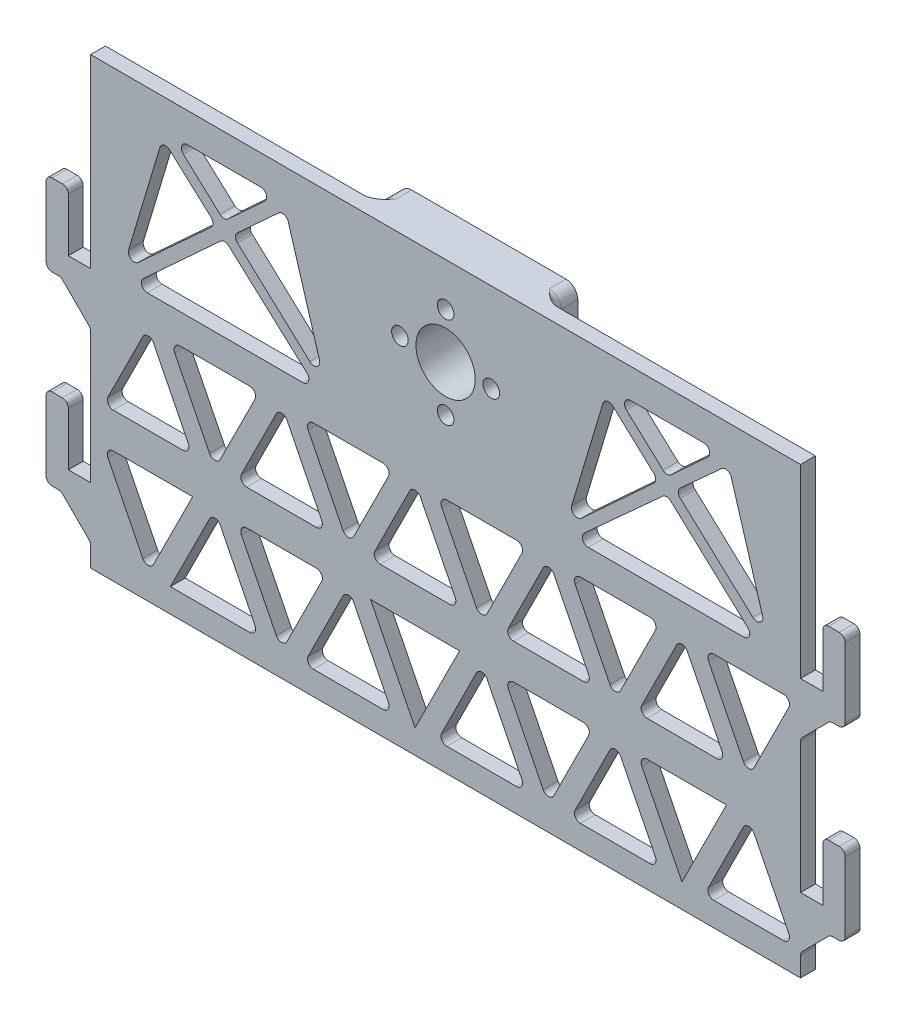
SolidWorks part; units mm, degrees
ref_plane "Front" through (0, 0, 0) normal (0, 0, 1) x (1, 0, 0)
ref_plane "Top" through (0, 0, 0) normal (0, 1, 0) x (1, 0, 0)
ref_plane "Right" through (0, 0, 0) normal (1, 0, 0) x (0, 0, -1)
sketch "Sketch1" plane through (0, 0, 0) normal (0, 0, 1) x (1, 0, 0)
  line L1 (0, 0) -> (-38.1, 0)
  line L2 (0, 0) -> (0, -38.1)
  line L3 (0, -38.1) -> (-38.1, -38.1)
  line L4 (-38.1, 0) -> (-38.1, -38.1)
  dimension "D1" = 38.1
  dimension "D2" = 38.1
extrude "Boss-Extrude1" add sketch "Sketch1" along normal blind 9.2583
sketch "Sketch2" plane through (0, 0, 9.2583) normal (0, 0, 1) x (1, 0, 0)
  line L0 (0, 0) -> (-38.1, 0) construction
  line L1 (0, -38.1) -> (0, 0) construction
  circle A0 centre (-19.05, -19.05) radius 6.35
  dimension "D1" = 12.7
  dimension "D2" = 19.05
  dimension "D3" = 19.05
extrude "Cut-Extrude1" cut sketch "Sketch2" against normal blind 10.8458
sketch "Sketch3" plane through (0, 0, 9.2583) normal (0, 0, 1) x (1, 0, 0)
  circle A0 centre (-19.05, -9.271) radius 1.778
  circle A1 centre (-19.05, -19.05) radius 6.35 construction
  dimension "D1" = 3.556
  dimension "D2" = 9.779
extrude "Cut-Extrude2" cut sketch "Sketch3" against normal blind 10.8458
pattern_circular "CirPattern1" count 4 over 360 about axis through (-19.05, -19.05, 9.2583) along (0, 0, 1) of "Cut-Extrude2"
sketch "Sketch4" plane through (0, 0, 9.2583) normal (0, 0, 1) x (1, 0, 0)
  line L1 (-38.1, 0) -> (-95.058, 0)
  line L2 (-38.1, 0) -> (-38.1, -95.2246)
  line L3 (-38.1, -95.2246) -> (-95.058, -95.2246)
  line L4 (-95.058, 0) -> (-95.058, -95.2246)
  line L5 (0, 0) -> (56.958, 0)
  line L6 (0, 0) -> (0, -95.2246)
  line L7 (0, -95.2246) -> (56.958, -95.2246)
  line L8 (56.958, 0) -> (56.958, -95.2246)
  dimension "D1" = 56.958
  dimension "D2" = 56.958
  dimension "D3" = 95.2246
  dimension "D4" = 95.2246
extrude "Boss-Extrude2" add sketch "Sketch4" against normal blind 3.175
sketch "Sketch5" plane through (0, 0, 6.0833) normal (0, 0, -1) x (-1, 0, 0)
  line L1 (0, -38.1) -> (38.1, -38.1)
  line L2 (0, -38.1) -> (0, -95.2246)
  line L3 (0, -95.2246) -> (38.1, -95.2246)
  line L4 (38.1, -38.1) -> (38.1, -95.2246)
extrude "Boss-Extrude3" add sketch "Sketch5" against normal blind 3.175
fillet "Fillet1" radius 2.54 4 edges at (-38.1, 0, 3.0416) (-38.1, -38.1, 3.0416) (0, -38.1, 3.0416) (0, 0, 3.0416)
fillet "Fillet2" radius 2.54 7 edges at (-0.7439, -0.7439, 6.0833) (-37.3561, -0.7439, 6.0833) (-38.1, -19.05, 6.0833) (-37.3561, -37.3561, 6.0833) (-19.05, -38.1, 6.0833) (-0.7439, -37.3561, 6.0833) (0, -19.05, 6.0833)
sketch "Sketch6" plane through (0, 0, 6.0833) normal (0, 0, -1) x (-1, 0, 0)
  line L0 (-56.958, -95.2246) -> (-56.958, 0) construction
  line L1 (-56.958, -39.6875) -> (-61.7205, -39.6875)
  line L2 (-56.958, -39.6875) -> (-56.958, -44.45)
  line L3 (-56.958, -44.45) -> (-66.483, -44.45)
  line L5 (-66.483, -26.9875) -> (-66.483, -44.45)
  line L8 (-66.483, -26.9875) -> (-61.7205, -26.9875)
  line L9 (-61.7205, -39.6875) -> (-61.7205, -26.9875)
  line L10 (-56.958, 0) -> (-1.8594, 0) construction
  point P3 (-59.3392, -39.6875)
  dimension "D1" = 4.7625
  dimension "D2" = 4.7625
  dimension "D3" = 4.7625
  dimension "D4" = 12.7
  dimension "D5" = 44.45
extrude "Boss-Extrude4" add sketch "Sketch6" against normal blind 3.175
sketch "Sketch7" plane through (0, 0, 6.0833) normal (0, 0, -1) x (-1, 0, 0)
  line L0 (-56.958, -84.1375) -> (-66.483, -84.1375)
  line L1 (-56.958, -95.2246) -> (-56.958, -44.45) construction
  line L2 (-66.483, -66.675) -> (-66.483, -84.1375)
  line L3 (-61.7205, -79.375) -> (-56.958, -79.375)
  line L4 (-61.7205, -79.375) -> (-61.7205, -66.675)
  line L5 (-61.7205, -66.675) -> (-66.483, -66.675)
  line L6 (-56.958, -79.375) -> (-56.958, -84.1375)
  line L7 (-66.483, -44.45) -> (-56.958, -44.45) construction
  dimension "D1" = 4.7625
  dimension "D2" = 4.7625
  dimension "D3" = 12.7
  dimension "D4" = 4.7625
  dimension "D5" = 22.225
extrude "Boss-Extrude5" add sketch "Sketch7" against normal blind 3.175
chamfer "Chamfer1" distance 6.35 angle 45 2 edges at (56.958, -84.1375, 7.6708) (56.958, -44.45, 7.6708)
fillet "Fillet3" radius 1.27 10 edges at (66.483, -26.9875, 7.6708) (61.7205, -26.9875, 7.6708) (66.483, -44.45, 7.6708) (63.308, -44.45, 7.6708) (56.958, -50.8, 7.6708) (66.483, -66.675, 7.6708) (66.483, -84.1375, 7.6708) (61.7205, -66.675, 7.6708) (56.958, -90.4875, 7.6708) (63.308, -84.1375, 7.6708)
ref_plane "Plane1" through (-19.05, 0, 0) normal (1, 0, 0) x (0, 0, -1)
mirror "Mirror2" about plane through (-19.05, 0, 0) normal (1, 0, 0) of "Boss-Extrude5", "Boss-Extrude4"
chamfer "Chamfer2" distance 6.35 angle 45 2 edges at (-95.058, -44.45, 7.6708) (-95.058, -84.1375, 7.6708)
fillet "Fillet4" radius 1.27 10 edges at (-95.058, -50.8, 7.6708) (-101.408, -44.45, 7.6708) (-104.583, -44.45, 7.6708) (-104.583, -26.9875, 7.6708) (-99.8205, -26.9875, 7.6708) (-99.8205, -66.675, 7.6708) (-104.583, -66.675, 7.6708) (-104.583, -84.1375, 7.6708) (-101.408, -84.1375, 7.6708) (-95.058, -90.4875, 7.6708)
sketch "Sketch8" plane through (0, 0, 6.0833) normal (0, 0, -1) x (-1, 0, 0)
  line L0 (-50.608, -38.1) -> (-6.158, -38.1)
  line L1 (-6.158, -38.1) -> (-15.683, -6.35)
  line L2 (-15.683, -6.35) -> (-41.083, -6.35)
  line L3 (-41.083, -6.35) -> (-50.608, -38.1)
  line L4 (-56.958, -39.6875) -> (-56.958, 0) construction
  line L5 (-56.958, 0) -> (-1.8594, 0) construction
  point P6 (-44.2524, -49.314)
  dimension "D1" = 44.45
  dimension "D2" = 6.35
  dimension "D3" = 6.35
  dimension "D4" = 31.75
  dimension "D5" = 25.4
  dimension "D6" = 9.525
extrude "Cut-Extrude3" cut sketch "Sketch8" against normal blind 4.7625
mirror "Mirror3" about plane through (-19.05, 0, 0) normal (1, 0, 0) of "Cut-Extrude3"
sketch "Sketch9" plane through (0, 0, 6.0833) normal (0, 0, -1) x (-1, 0, 0)
  line L0 (-41.5391, -7.8705) -> (-8.19, -38.1)
  line L1 (-41.083, -6.35) -> (-50.608, -38.1) construction
  line L2 (-50.608, -38.1) -> (-6.158, -38.1) construction
  line L3 (-8.19, -38.1) -> (-6.158, -38.1)
  line L4 (-6.158, -38.1) -> (-6.6141, -36.5795)
  line L5 (-6.158, -38.1) -> (-15.683, -6.35) construction
  line L6 (-6.6141, -36.5795) -> (-39.4955, -6.35)
  line L7 (-15.683, -6.35) -> (-41.083, -6.35) construction
  line L8 (-39.4955, -6.35) -> (-41.083, -6.35)
  line L9 (-41.083, -6.35) -> (-41.5391, -7.8705)
  dimension "D1" = 2.032
  dimension "D2" = 1.5875
  dimension "D3" = 1.5875
  dimension "D4" = 1.5875
extrude "Boss-Extrude6" add sketch "Sketch9" against normal blind 3.175
sketch "Sketch10" plane through (0, 0, 6.0833) normal (0, 0, -1) x (-1, 0, 0)
  line L0 (-50.608, -38.1) -> (-48.068, -38.1)
  line L1 (-50.608, -38.1) -> (-8.19, -38.1) construction
  line L2 (-48.068, -38.1) -> (-15.2268, -7.8705)
  line L3 (-6.6141, -36.5795) -> (-15.683, -6.35) construction
  line L4 (-15.2268, -7.8705) -> (-15.683, -6.35)
  line L5 (-15.683, -6.35) -> (-17.2705, -6.35)
  line L6 (-15.683, -6.35) -> (-39.4955, -6.35) construction
  line L7 (-17.2705, -6.35) -> (-50.1518, -36.5795)
  line L8 (-41.5391, -7.8705) -> (-50.608, -38.1) construction
  line L9 (-50.1518, -36.5795) -> (-50.608, -38.1)
  dimension "D1" = 2.54
  dimension "D2" = 1.5875
  dimension "D3" = 1.5875
  dimension "D4" = 1.5875
extrude "Boss-Extrude7" add sketch "Sketch10" against normal blind 3.175
mirror "Mirror4" about plane through (-19.05, 0, 0) normal (1, 0, 0) of "Boss-Extrude7", "Boss-Extrude6"
fillet "Fillet5" radius 1.27 12 edges at (15.2268, -7.8705, 7.6708) (17.2705, -6.35, 7.6708) (39.4955, -6.35, 7.6708) (41.5391, -7.8705, 7.6708) (50.1518, -36.5795, 7.6708) (26.5273, -18.2723, 7.6708) (30.1519, -18.1925, 7.6708) (28.383, -16.5663, 7.6708) (6.6141, -36.5795, 7.6708) (8.19, -38.1, 7.6708) (48.068, -38.1, 7.6708) (28.282, -19.8875, 7.6708)
fillet "Fillet6" radius 1.27 12 edges at (-79.6391, -7.8705, 7.6708) (-88.2518, -36.5795, 7.6708) (-86.168, -38.1, 7.6708) (-68.2519, -18.1925, 7.6708) (-66.382, -19.8875, 7.6708) (-77.5955, -6.35, 7.6708) (-55.3705, -6.35, 7.6708) (-66.483, -16.5663, 7.6708) (-53.3268, -7.8705, 7.6708) (-64.6273, -18.2723, 7.6708) (-44.7141, -36.5795, 7.6708) (-46.29, -38.1, 7.6708)
sketch "Sketch11" plane through (0, 0, 6.0833) normal (0, 0, -1) x (-1, 0, 0)
  line L0 (-55.3705, -44.45) -> (-36.3205, -44.45)
  line L1 (-36.3205, -44.45) -> (-45.8455, -63.5)
  line L2 (-45.8455, -63.5) -> (-55.3705, -44.45)
  line L3 (-44.813, -38.1) -> (-11.482, -38.1) construction
  line L4 (-56.958, -79.375) -> (-56.958, -51.3261) construction
  line L5 (-41.083, -63.5) -> (-31.558, -44.45)
  line L6 (-31.558, -44.45) -> (-22.033, -63.5)
  line L7 (-22.033, -63.5) -> (-41.083, -63.5)
  point P9 (0, 0)
  point P12 (-37.2302, -62.9106)
  dimension "D1" = 6.35
  dimension "D2" = 19.05
  dimension "D3" = 19.05
  dimension "D4" = 9.525
  dimension "D5" = 1.5875
  dimension "D6" = 19.05
  dimension "D7" = 19.05
  dimension "D8" = 9.525
  dimension "D9" = 4.7625
extrude "Cut-Extrude4" cut sketch "Sketch11" against normal blind 3.175
pattern_linear "LPattern1" count 5 spacing 28.575 along (-1, 0, 0) of "Cut-Extrude4"
ref_plane "Plane2" through (0, -67.2846, 0) normal (0, -1, 0) x (-1, 0, 0)
mirror "Mirror5" about plane through (0, -67.2846, 0) normal (0, -1, 0) of "LPattern1"
fillet "Fillet7" radius 1.27 53 edges at (-92.267, -71.0692, 7.6708) (-68.4545, -71.0692, 7.6708) (-82.742, -44.45, 7.6708) (-77.9795, -44.45, 7.6708) (-92.267, -63.5, 7.6708) (-58.9295, -44.45, 7.6708) (-58.9295, -90.1192, 7.6708) (-73.217, -63.5, 7.6708) (-68.4545, -63.5, 7.6708) (-82.742, -90.1192, 7.6708) (-54.167, -90.1192, 7.6708) (-44.642, -71.0692, 7.6708) (-44.642, -63.5, 7.6708) (-54.167, -44.45, 7.6708) (-63.692, -63.5, 7.6708) (-63.692, -71.0692, 7.6708) (-49.4045, -44.45, 7.6708) (-49.4045, -90.1192, 7.6708) (-30.3545, -90.1192, 7.6708) (-39.8795, -71.0692, 7.6708) (-30.3545, -44.45, 7.6708) (-39.8795, -63.5, 7.6708) (-16.067, -63.5, 7.6708) (-35.117, -63.5, 7.6708) (-25.592, -44.45, 7.6708) (-11.3045, -63.5, 7.6708) (-20.8295, -44.45, 7.6708) (-11.3045, -71.0692, 7.6708) (-1.7795, -90.1192, 7.6708) (-20.8295, -90.1192, 7.6708) (2.983, -90.1192, 7.6708) (-6.542, -71.0692, 7.6708) (2.983, -44.45, 7.6708) (-6.542, -63.5, 7.6708) (12.508, -63.5, 7.6708) (12.508, -71.0692, 7.6708) (17.2705, -71.0692, 7.6708) (26.7955, -90.1192, 7.6708) (55.3705, -90.1192, 7.6708) (7.7455, -90.1192, 7.6708) (36.3205, -90.1192, 7.6708) (22.033, -63.5, 7.6708) (17.2705, -63.5, 7.6708) (7.7455, -44.45, 7.6708) (22.033, -71.0692, 7.6708) (45.8455, -71.0692, 7.6708) (31.558, -44.45, 7.6708) (41.083, -63.5, 7.6708) (45.8455, -63.5, 7.6708) (36.3205, -44.45, 7.6708) (-1.7795, -44.45, 7.6708) (26.7955, -44.45, 7.6708) (55.3705, -44.45, 7.6708)
